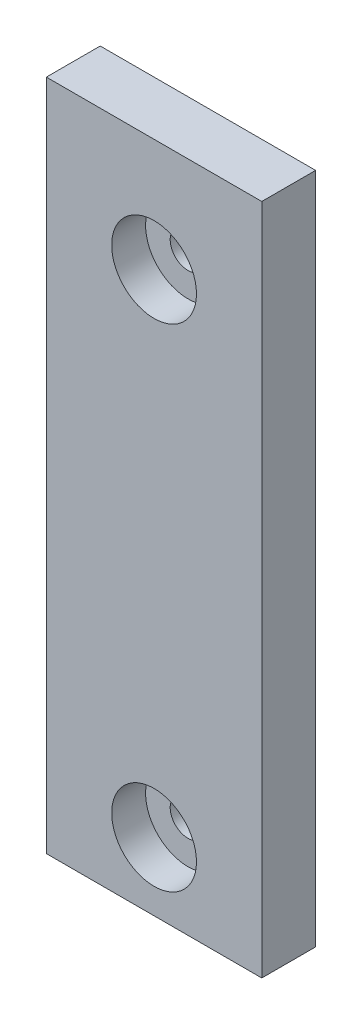
SolidWorks part; units mm, degrees
material "PTFE (general)"
ref_plane "Front Plane" through (0, 0, 0) normal (0, 0, 1) x (1, 0, 0)
ref_plane "Top Plane" through (0, 0, 0) normal (0, 1, 0) x (1, 0, 0)
ref_plane "Right Plane" through (0, 0, 0) normal (1, 0, 0) x (0, 0, -1)
sketch "Sketch1" plane through (0, 0, 0) normal (0, 1, 0) x (1, 0, 0)
  line L1 (19.7561, -3.1163) -> (45.1561, -3.1163)
  line L2 (19.7561, -3.1163) -> (19.7561, 3.2337)
  line L3 (19.7561, 3.2337) -> (45.1561, 3.2337)
  line L4 (45.1561, -3.1163) -> (45.1561, 3.2337)
  dimension "D1" = 25.4
  dimension "D2" = 6.35
extrude "Boss-Extrude1" add sketch "Sketch1" along normal blind 100
sketch "Sketch2" plane through (0, 0, 3.1163) normal (0, 0, 1) x (1, 0, 0)
  line L0 (32.4561, 100) -> (32.4561, 0) construction
  line L1 (19.7561, 100) -> (45.1561, 100) construction
  line L2 (19.7561, 0) -> (45.1561, 0) construction
  circle A0 centre (32.4561, 81.7) radius 2.1
  circle A1 centre (32.4561, 23.71) radius 2.1
  circle A2 centre (32.4561, 81.7) radius 5
  circle A3 centre (32.4561, 23.71) radius 5
  dimension "D1" = 81.7
  dimension "D2" = 23.71
  dimension "D3" = 4.2
  dimension "D4" = 4.2
  dimension "D5" = 10
  dimension "D6" = 10
extrude "Cut-Extrude1" cut sketch "Sketch2" against normal through all contours A0 | A1
extrude "Cut-Extrude2" cut sketch "Sketch2<3>" against normal blind 4 contours A2
sketch "Sketch2<3>" plane through (0, 0, 3.1163) normal (0, 0, 1) x (1, 0, 0) same geometry as "Sketch2"
extrude "Cut-Extrude3" cut sketch "Sketch2<4>" against normal blind 4 contours A3
sketch "Sketch2<4>" plane through (0, 0, 3.1163) normal (0, 0, 1) x (1, 0, 0) same geometry as "Sketch2"
sketch "Sketch5" plane through (0, 0, 3.1163) normal (0, 0, 1) x (1, 0, 0)
  line L0 (45.1561, 100) -> (45.1561, 0) construction
  line L1 (19.7561, 100) -> (45.1561, 100)
  line L2 (19.7561, 100) -> (19.7561, 95)
  line L3 (19.7561, 95) -> (45.1561, 95)
  line L4 (45.1561, 100) -> (45.1561, 95)
  line L6 (19.7561, 0) -> (45.1561, 0)
  line L7 (19.7561, 0) -> (19.7561, 12)
  line L8 (19.7561, 12) -> (45.1561, 12)
  line L9 (45.1561, 0) -> (45.1561, 12)
  dimension "D1" = 5
  dimension "D2" = 12
extrude "Cut-Extrude4" cut sketch "Sketch5" against normal through all
sketch "Sketch6" plane through (0, 0, 3.1163) normal (0, 0, 1) x (1, 0, 0)
  line L0 (45.1561, 95) -> (45.1561, 12) construction
  line L1 (19.7561, 12) -> (45.1561, 12)
  line L2 (19.7561, 12) -> (19.7561, 15.7)
  line L3 (19.7561, 15.7) -> (45.1561, 15.7)
  line L4 (45.1561, 12) -> (45.1561, 15.7)
  dimension "D1" = 3.7
extrude "Cut-Extrude5" cut sketch "Sketch6" against normal through all
